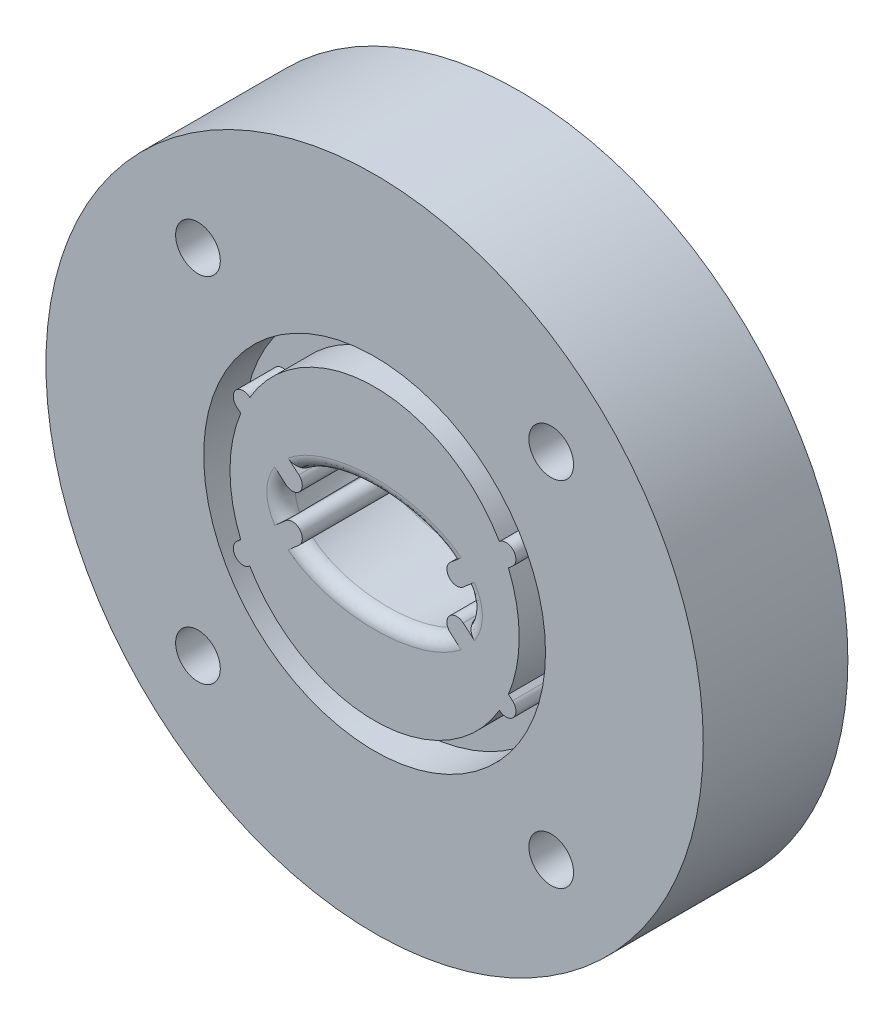
SolidWorks part; units mm, degrees
ref_plane "Plan de face" through (0, 0, 0) normal (0, 0, 1) x (1, 0, 0)
ref_plane "Plan de dessus" through (0, 0, 0) normal (0, 1, 0) x (1, 0, 0)
ref_plane "Plan de droite" through (0, 0, 0) normal (1, 0, 0) x (0, 0, -1)
sketch "Esquisse1" plane through (0, 0, 0) normal (0, 0, 1) x (1, 0, 0)
  circle A0 centre (0, 0) radius 25
  circle A1 centre (-13.435, 13.435) radius 1.7
  circle A2 centre (13.435, 13.435) radius 1.7
  circle A3 centre (13.435, -13.435) radius 1.7
  circle A4 centre (-13.435, -13.435) radius 1.7
  point P19 (0, 0)
  dimension "D1" = 50
  dimension "D5" = 19
  dimension "D6" = 3.4
  dimension "D4" = 4
extrude "Boss.-Extru.1" add sketch "Esquisse1" along normal blind 11
sketch "Esquisse4" plane through (0, 0, 11) normal (0, 0, 1) x (1, 0, 0)
  ellipse E0 centre (0, 0) end of major axis (-7, 0) minor radius 4
  dimension "D1" = 8
  dimension "D2" = 14
sketch "Esquisse5" plane through (0, 0, 0) normal (0, 0, -1) x (-1, 0, 0)
  ellipse E0 centre (0, 0) end of major axis (9, 0) minor radius 4
  dimension "D1" = 8
  dimension "D2" = 18
loft "Enlèvement de matière-Lissage1" cut profiles "Esquisse5", "Esquisse4" connector at (0.0922, -3.9998, 0) connector at (-0.1656, -3.9989, 11)
sketch "Esquisse2" plane through (0, 0, 11) normal (0, 0, 1) x (1, 0, 0)
  circle A0 centre (0, 0) radius 13
  circle A1 centre (0, 0) radius 11
  dimension "D1" = 22
  dimension "D2" = 26
extrude "Enlèv. mat.-Extru.1" cut sketch "Esquisse2" against normal blind 3
ref_axis "Axe1" through (0, 0, 0.0524) along (0, 0, 1)
ref_plane "Plan1" through (0, 0, 0) normal (1, 0, 0) x (0, 0, -1)
fillet "Congé1" radius 1 1 edges at (-7, 0, 11)
sketch "Esquisse6" plane through (0, 0, 0) normal (0, 0, -1) x (-1, 0, 0)
  circle A0 centre (0, 0) radius 11
  dimension "D1" = 22
extrude "Enlèv. mat.-Extru.2" cut sketch "Esquisse6" against normal blind 3
fillet "Congé2" radius 0.5 1 edges at (-11, 0, 3)
fillet "Congé3" radius 0.5 1 edges at (-0.8219, 3.9812, 3)
sketch "Esquisse8" plane through (0, 0, 11) normal (0, 0, 1) x (1, 0, 0)
  line L0 (-6.5, 2) -> (6.5, 2) construction
  line L1 (6.5, 2) -> (6.5, -2) construction
  line L2 (6.5, -2) -> (-6.5, -2) construction
  line L3 (-6.5, 2) -> (-6.5, -2) construction
  line L4 (-6.25, 1.75) -> (-6.25, 2) construction
  line L5 (-6.25, 1.75) -> (-6.5, 1.75) construction
  line L6 (-6.25, -1.75) -> (-6.5, -1.75) construction
  line L7 (-6.25, -1.75) -> (-6.25, -2) construction
  line L8 (6.25, 1.75) -> (6.25, 2) construction
  line L9 (6.25, 1.75) -> (6.5, 1.75) construction
  line L10 (6.25, -1.75) -> (6.5, -1.75) construction
  line L11 (6.25, -1.75) -> (6.25, -2) construction
  line L12 (6.5, 0) -> (-6.5, 0) construction
  circle A0 centre (-6.25, 1.75) radius 0.25
  circle A1 centre (-6.25, -1.75) radius 0.25
  circle A2 centre (6.25, 1.75) radius 0.25
  circle A3 centre (6.25, -1.75) radius 0.25
extrude "Boss.-Extru.4" add sketch "Esquisse8" against normal blind 10
sketch "Esquisse9" plane through (0, 0, 1) normal (0, 0, -1) x (-1, 0, 0)
sketch "Esquisse10" plane through (0, 0, 11) normal (0, 0, 1) x (1, 0, 0)
  line L0 (-10, 0) -> (10, 0) construction
  line L1 (10, 0) -> (10, 5) construction
  line L2 (10, 5) -> (-10, 5) construction
  line L3 (-10, 5) -> (-10, 0) construction
  line L4 (6.5, -2) -> (-6.5, -2) construction
  line L5 (-6.5, 2) -> (6.5, 2) construction
  line L6 (6.5, 2) -> (6.5, -2) construction
  line L7 (6.5, 0) -> (-6.5, 0) construction
  line L8 (9.2495, -0.5365) -> (9.2495, 3.4635) construction
  line L9 (10, 0) -> (10, -5) construction
  line L10 (10, -5) -> (-10, -5) construction
  line L11 (-10, -5) -> (-10, 0) construction
  line L12 (-6.25, -1.75) -> (-10, -5) construction
  line L13 (-5.7588, -2.3168) -> (-9.5088, -5.5668)
  line L14 (-6.7412, -1.1832) -> (-10.4912, -4.4332)
  line L15 (-6.25, 1.75) -> (-10, 5) construction
  line L16 (-6.7412, 1.1832) -> (-10.4912, 4.4332)
  line L17 (-5.7588, 2.3168) -> (-9.5088, 5.5668)
  line L18 (10, -5) -> (6.25, -1.75) construction
  line L19 (9.5088, -5.5668) -> (5.7588, -2.3168)
  line L20 (10.4912, -4.4332) -> (6.7412, -1.1832)
  line L21 (10, 5) -> (6.25, 1.75) construction
  line L22 (10.4912, 4.4332) -> (6.7412, 1.1832)
  line L23 (9.5088, 5.5668) -> (5.7588, 2.3168)
  arc A0 (-5.7588, -2.3168) -> (-6.7412, -1.1832) centre (-6.25, -1.75) ccw
  arc A1 (-10.4912, -4.4332) -> (-9.5088, -5.5668) centre (-10, -5) ccw
  arc A2 (-6.7412, 1.1832) -> (-5.7588, 2.3168) centre (-6.25, 1.75) ccw
  arc A3 (-9.5088, 5.5668) -> (-10.4912, 4.4332) centre (-10, 5) ccw
  arc A4 (9.5088, -5.5668) -> (10.4912, -4.4332) centre (10, -5) ccw
  arc A5 (6.7412, -1.1832) -> (5.7588, -2.3168) centre (6.25, -1.75) ccw
  arc A6 (10.4912, 4.4332) -> (9.5088, 5.5668) centre (10, 5) ccw
  arc A7 (5.7588, 2.3168) -> (6.7412, 1.1832) centre (6.25, 1.75) ccw
  point P12 (0, 0)
  point P18 (-8.125, -3.375)
  point P24 (-8.125, 3.375)
  point P31 (8.125, -3.375)
  point P38 (8.125, 3.375)
extrude "Boss.-Extru.6" add sketch "Esquisse10" against normal blind 10
equation "\"9.5.00mm\"=6"
